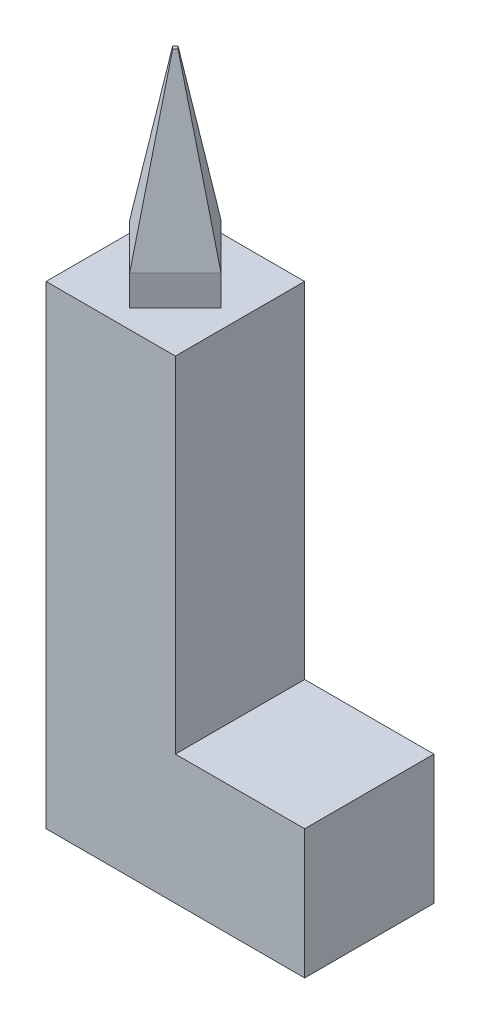
SolidWorks part; units mm, degrees
ref_plane "正面" through (0, 0, 0) normal (0, 0, 1) x (1, 0, 0)
ref_plane "平面" through (0, 0, 0) normal (0, 1, 0) x (1, 0, 0)
ref_plane "右側面" through (0, 0, 0) normal (1, 0, 0) x (0, 0, -1)
other "重心"
sketch "ｽｹｯﾁ1" plane through (0, 0, 0) normal (0, 1, 0) x (1, 0, 0)
  line L1 (0, 0) -> (60, 0)
  line L2 (0, 0) -> (0, -30)
  line L3 (0, -30) -> (60, -30)
  line L4 (60, 0) -> (60, -30)
  dimension "D1" = 60
  dimension "D2" = 30
extrude "ﾎﾞｽ - 押し出し1" add sketch "ｽｹｯﾁ1" along normal blind 30
sketch "ｽｹｯﾁ2" plane through (0, 30, 0) normal (0, 1, 0) x (1, 0, 0)
  line L0 (0, -30) -> (60, -30) construction
  line L1 (0, 0) -> (30, 0)
  line L2 (0, 0) -> (0, -30)
  line L3 (0, -30) -> (30, -30)
  line L4 (30, 0) -> (30, -30)
  dimension "D1" = 30
extrude "ﾎﾞｽ - 押し出し2" add sketch "ｽｹｯﾁ2" along normal blind 80
sketch "ｽｹｯﾁ3" plane through (0, 110, 0) normal (0, 1, 0) x (1, 0, 0)
  line L1 (4.3934, -15) -> (15, -4.3934)
  line L2 (4.3934, -15) -> (15, -25.6066)
  line L3 (15, -25.6066) -> (25.6066, -15)
  line L4 (15, -4.3934) -> (25.6066, -15)
  line L5 (4.3934, -15) -> (25.6066, -15) construction
  line L9 (15, -4.3934) -> (15, -25.6066) construction
  line L13 (30, -15) -> (0, -15) construction
  line L14 (30, -30) -> (30, 0) construction
  line L15 (0, 0) -> (0, -30) construction
  line L16 (15, 0) -> (15, -30) construction
  line L17 (30, 0) -> (0, 0) construction
  line L18 (0, -30) -> (30, -30) construction
  dimension "D1" = 15
extrude "ﾎﾞｽ - 押し出し3" add sketch "ｽｹｯﾁ3" along normal blind 47
chamfer "面取り1" distance 40 angle 10 4 edges at (9.6967, 157, 9.6967) (20.3033, 157, 9.6967) (20.3033, 157, 20.3033) (9.6967, 157, 20.3033) first distance on face at (9.6967, 133.5, 9.6967) first distance on face at (20.3033, 133.5, 9.6967) first distance on face at (20.3033, 133.5, 20.3033) first distance on face at (9.6967, 133.5, 20.3033)
ref_plane "平面1" through (15, 0, 0) normal (-1, 0, 0) x (0, 0, 1)
ref_plane "平面2" through (0, 0, 15) normal (0, 0, 1) x (1, 0, 0)
ref_plane "平面3" through (0, 78.5, 0) normal (0, -1, 0) x (-1, 0, 0)
ref_axis "軸1" through (-3, 78.5, 15) along (1, 0, 0)
ref_point "点1"
ref_axis "軸2" through (15, -5.5, 15) along (0, 1, 0)
